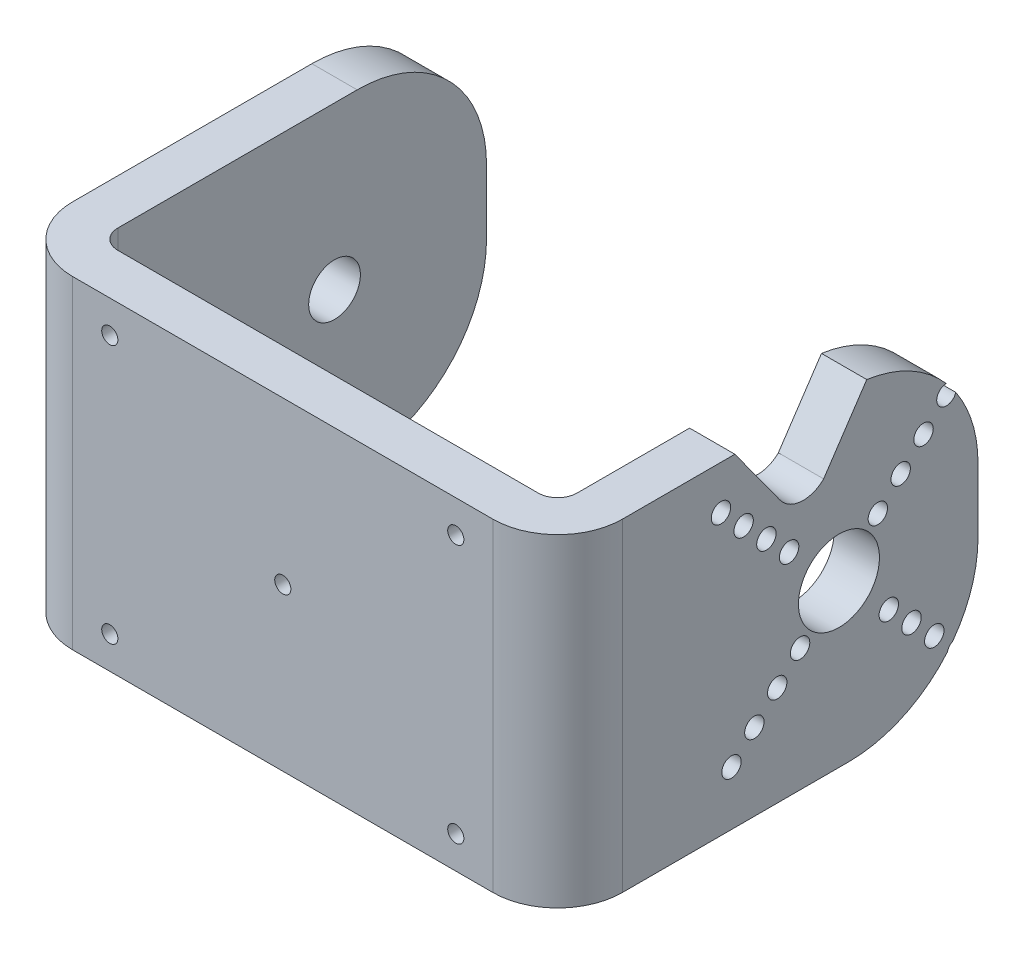
SolidWorks part; units mm, degrees
note: The reader was unsure of these and kept them because the rebuilt part matched: shared geometry of "Sketch6<3>".
ref_plane "Front Plane" through (0, 0, 0) normal (0, 0, 1) x (1, 0, 0)
ref_plane "Top Plane" through (0, 0, 0) normal (0, 1, 0) x (1, 0, 0)
ref_plane "Right Plane" through (0, 0, 0) normal (1, 0, 0) x (0, 0, -1)
sketch "Sketch1" plane through (0, 0, 0) normal (0, 1, 0) x (1, 0, 0)
  line L0 (-56.3757, 67.498) -> (-56.3757, 10.498)
  line L1 (28.6243, 65.498) -> (28.6243, 10.498)
  line L2 (-46.3757, 0.498) -> (18.6243, 0.498)
  line L3 (-49.3757, 67.498) -> (-49.3757, 10.498)
  line L4 (-46.3757, 7.498) -> (18.6243, 7.498)
  line L5 (21.6243, 65.498) -> (21.6243, 10.498)
  line L6 (21.6243, 65.498) -> (28.6243, 65.498)
  line L7 (-49.3757, 67.498) -> (-56.3757, 67.498)
  arc A0 (-56.3757, 10.498) -> (-46.3757, 0.498) centre (-46.3757, 10.498) ccw
  arc A1 (18.6243, 0.498) -> (28.6243, 10.498) centre (18.6243, 10.498) ccw
  arc A2 (-49.3757, 10.498) -> (-46.3757, 7.498) centre (-46.3757, 10.498) ccw
  arc A3 (18.6243, 7.498) -> (21.6243, 10.498) centre (18.6243, 10.498) ccw
  dimension "D1" = 10
  dimension "D3" = 10
  dimension "D2" = 85
  dimension "D4" = 60
  dimension "D6" = 65
  dimension "D5" = 7
extrude "Boss-Extrude1" add sketch "Sketch1" along normal blind 50
fillet "Fillet2" radius 20 4 edges at (-52.8757, 50, -67.498) (-52.8757, 0, -67.498) (25.1243, 0, -65.498) (25.1243, 50, -65.498)
sketch "Sketch6" plane through (28.6243, 0, 0) normal (1, 0, 0) x (0, 0, -1)
  line L0 (65.498, 30) -> (65.498, 20) construction
  line L1 (85.3454, 25) -> (-15.2119, 25) construction
  circle A0 centre (43.998, 25) radius 4
  point P5 (65.498, 25)
  line B0 (24.9389, 5.9409) -> (62.2034, 43.2054) construction
  line B1 (-1270.3531, -1372.4722) -> (-843.732, -945.8511) construction
  line B2 (25.0731, 5.8923) -> (62.4233, 42.9855) construction
  line B3 (-116.3936, 133.0666) -> (-63.3606, 186.0996) construction
  line B4 (39.5703, 29.4276) -> (48.4256, 20.5724) construction
  line B5 (25.7546, 43.2434) -> (64.951, 4.047) construction
  circle B6 centre (25.7546, 43.2434) radius 1.5
  circle B7 centre (29.2548, 39.7432) radius 1.5
  circle B8 centre (32.7762, 36.2218) radius 1.5
  circle B9 centre (36.2905, 32.7075) radius 1.5
  circle B10 centre (37.9876, 18.9896) radius 1.5
  circle B11 centre (34.452, 15.4541) radius 1.5
  circle B12 centre (30.9165, 11.9185) radius 1.5
  circle B13 centre (27.381, 8.383) radius 1.5
  circle B14 centre (43.998, 25) radius 6.2616
  circle B15 centre (-2.2988, -9.2742) radius 3.25 construction
  circle B16 centre (9.722, -21.295) radius 3.25 construction
  circle B17 centre (50.7342, 43.7588) radius 3.25 construction
  circle B18 centre (62.755, 31.738) radius 3.25 construction
  circle B19 centre (50.0084, 31.0104) radius 1.5
  circle B20 centre (53.5439, 34.5459) radius 1.5
  circle B21 centre (57.0795, 38.0815) radius 1.5
  circle B22 centre (60.615, 41.617) radius 1.5
  circle B23 centre (62.2413, 6.7566) radius 1.5
  circle B24 centre (58.7412, 10.2568) radius 1.5
  circle B25 centre (55.2198, 13.7782) radius 1.5
  circle B26 centre (51.7054, 17.2925) radius 1.5
  dimension "D2" = 8
  dimension "D1" = 21.5
sketch_block_instance "Block-Sketch2-2"
sketch_block "Block-Sketch2" parameters "D2"=3, "D3"=3, "D4"=3, "D5"=3, "D6"=3, "D7"=3, "D8"=3, "D9"=3, "D10"=6.5, "D11"=6.5, "D12"=6.5, "D1"=52.7, "D13"=75, "D14"=17, "D15"=75, "D16"=8.5, "D17"=13.5, "D18"=18.5, "D19"=23.5, "D20"=10.9, "D21"=15.87, "D22"=20.85, "D23"=25.8
extrude "Cut-Extrude2" cut sketch "Sketch6" against normal blind 28.4 contours A0 L1 | L1 A0 | L1 B14 A0 | B14 L1 A0 | B9 | B8 | B7 | B6 | B19 | B20 | B21 | B22 | B26 | B25 | B24 | B23 | B10 | B11 | B12 | B13
extrude "Cut-Extrude3" cut sketch "Sketch6<3>" against normal blind 136.4 contours L1 A0 | A0 L1
sketch "Sketch6<3>" plane through (28.6243, 0, 0) normal (1, 0, 0) x (0, 0, -1) same geometry as "Sketch6"
sketch "Sketch7" plane through (28.6243, 0, 0) normal (1, 0, 0) x (0, 0, -1)
  line L0 (27.9014, 50) -> (34.8899, 40.3636)
  line L1 (10.498, 50) -> (45.498, 50) construction
  line L2 (41.6295, 39.8302) -> (48.2964, 49.8032)
  arc A0 (34.8899, 40.3636) -> (41.6295, 39.8302) centre (38.4873, 42.9724) ccw
  arc A1 (65.498, 30) -> (62.0594, 41.2125) centre (45.498, 30) ccw construction
  arc M16 (65.498, 30) -> (62.0594, 41.2125) centre (45.498, 30) ccw
  line M17 (45.498, 50) -> (10.498, 50)
extrude "Cut-Extrude4" cut sketch "Sketch7" against normal blind 26.4 and the other way through all contours L0 A0 L2 M16 M17
sketch "Sketch8" plane through (0, 0, -0.498) normal (0, 0, 1) x (1, 0, 0)
  line L0 (-46.3757, 25) -> (18.6243, 25) construction
  line L1 (-46.3757, 50) -> (-46.3757, 0) construction
  line L2 (18.6243, 50) -> (18.6243, 0) construction
  line L3 (-13.8757, 6.2475) -> (-13.8757, 55.8206) construction
  circle A0 centre (-40.6257, 45) radius 1.25
  circle A1 centre (12.8743, 45) radius 1.25
  circle A2 centre (-13.8757, 25) radius 1.25
  circle A3 centre (-40.6257, 5) radius 1.25
  circle A4 centre (12.8743, 5) radius 1.25
  point P15 (-13.8757, 25)
  dimension "D1" = 2.5
  dimension "D2" = 2.5
  dimension "D3" = 2.5
  dimension "D4" = 2.5
  dimension "D5" = 2.5
  dimension "D6" = 40
  dimension "D7" = 53.5
extrude "Cut-Extrude5" cut sketch "Sketch8" against normal blind 100
equation "\"D3@Sketch1\"=\"D1@Sketch1\""
equation "\"D2@Sketch8\"=\"D1@Sketch8\""
equation "\"D3@Sketch8\"=\"D2@Sketch8\""
equation "\"D4@Sketch8\"=\"D3@Sketch8\""
equation "\"D5@Sketch8\"=\"D3@Sketch8\""
